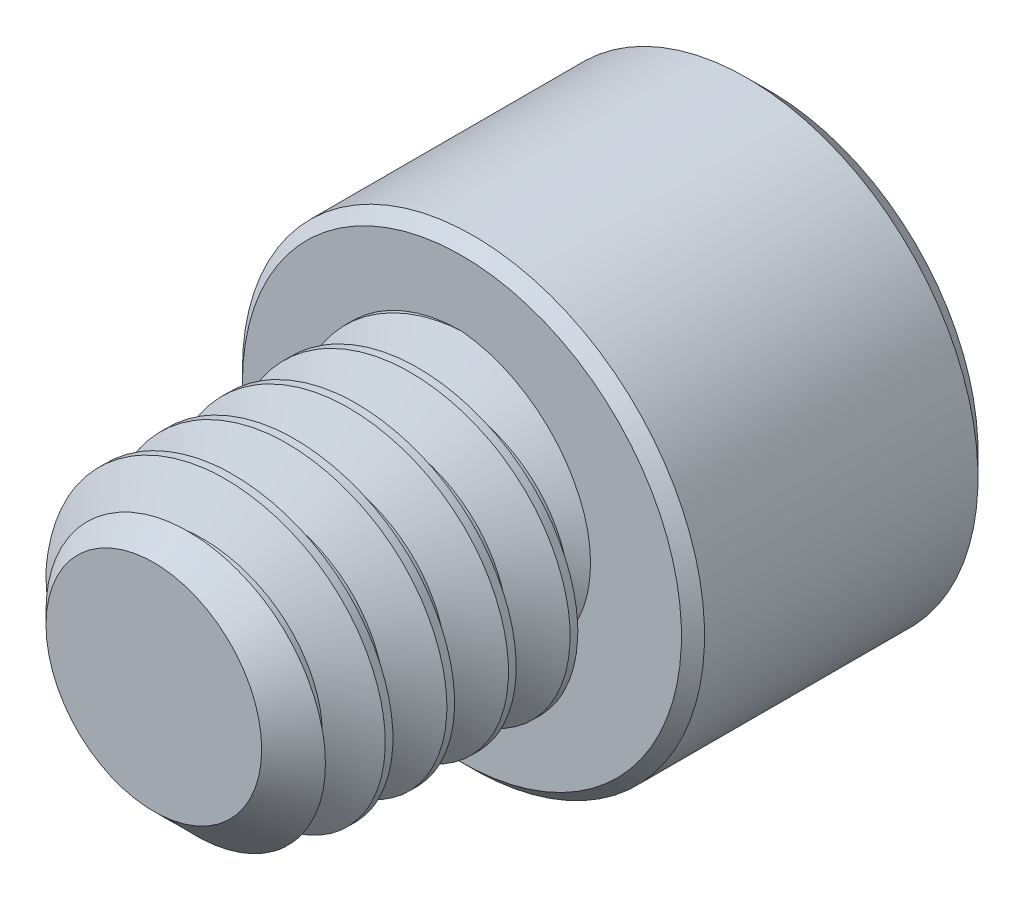
SolidWorks part; units mm, degrees
ref_plane "Front Plane" through (0, 0, 0) normal (0, 0, 1) x (1, 0, 0)
ref_plane "Top Plane" through (0, 0, 0) normal (0, 1, 0) x (1, 0, 0)
ref_plane "Right Plane" through (0, 0, 0) normal (1, 0, 0) x (0, 0, -1)
sketch "Sketch0" plane through (0, 0, 0) normal (1, 0, 0) x (0, 0, -1)
  line L0 (0, 0) -> (6.35, 0) construction
  point P2 (12.7, 0)
  point P4 (0, 0)
  dimension "D1" = 6.35
  dimension "D2" = 6.35
  dimension "Min Thread" = 0
sketch "Sketch1" plane through (0, 0, 0) normal (0, 0, 1) x (1, 0, 0)
  circle A0 centre (0, 0) radius 3.175
  dimension "OD" = 6.35
extrude "Extrude1" add sketch "Sketch1" against normal blind 6.35
sketch "Sketch2" plane through (0, 0, 0) normal (0, 0, 1) x (1, 0, 0)
  circle A0 centre (0, 0) radius 3.175 construction
  circle A1 centre (0, 0) radius 3.175
curve "Helix/Spiral1" pitch 1.27 height 7.62 turns 6 parameters "pitch"=1.27
chamfer "Chamfer3" distance 0.9525 angle 45 1 edges at (3.175, 0, 0)
sketch "Sketch3" plane through (0, 0, 0) normal (1, 0, 0) x (0, 0, -1)
  line L0 (-1.1113, 3.175) -> (-0.635, 2.3501)
  line L1 (-0.635, 2.3501) -> (-0.4763, 2.3501)
  line L2 (-0.4763, 2.3501) -> (0, 3.175)
  line L3 (-1.1113, 3.175) -> (0, 3.175)
  line L4 (-0.5556, 3.175) -> (-0.5556, 2.3501) construction
  line L5 (-0.8731, 2.7626) -> (-0.2381, 2.7626) construction
  line L6 (0, 3.175) -> (0, -3.175) construction
  dimension "D1" = 0.1588
  dimension "D2" = 0.635
  dimension "D3" = 60
sweep "Cut-Sweep1" cut profiles "Sketch3" path "Helix/Spiral1"
sketch "Sketch5" plane through (0, 0, 0) normal (1, 0, 0) x (0, 0, -1)
  line L0 (6.35, -2.3728) -> (6.35, 2.2654) construction
  line L1 (6.35, 3.175) -> (0, 3.175)
  line L2 (6.35, 3.175) -> (6.35, 0)
  line L3 (6.35, 0) -> (-1.1556, 0)
  line L4 (0, 0) -> (6.35, 0) construction
  line L5 (0, 3.175) -> (-1.1556, 0)
  line L6 (0, 0) -> (8.89, 0) construction
  dimension "D1" = 70
  dimension "D3" = 2.54
revolve "partially thread" [suppressed] add sketch "Sketch5" angle 360 about L6
sketch "Sketch6" plane through (0, 0, -6.35) normal (0, 0, -1) x (-1, 0, 0)
  circle A0 centre (0, 0) radius 4.7625
  dimension "head dia" = 9.525
extrude "Extrude2" add sketch "Sketch6" along normal blind 6.35
sketch "Sketch7" plane through (0, 0, -12.7) normal (0, 0, -1) x (-1, 0, 0)
  line L1 (0, 2.7496) -> (-2.3813, 1.3748)
  line L2 (-2.3813, 1.3748) -> (-2.3813, -1.3748)
  line L3 (-2.3813, -1.3748) -> (0, -2.7496)
  line L4 (0, -2.7496) -> (2.3813, -1.3748)
  line L5 (2.3813, -1.3748) -> (2.3813, 1.3748)
  line L6 (2.3813, 1.3748) -> (0, 2.7496)
  circle A0 centre (0, 0) radius 2.3813 construction
  dimension "hex dia" = 4.7625
extrude "Cut-Extrude1" cut sketch "Sketch7" against normal blind 3.5719
sketch "Sketch8" plane through (0, 0, -12.7) normal (0, 0, -1) x (-1, 0, 0)
  circle A0 centre (0, 0) radius 2.7496
extrude "Cut-Extrude2" cut sketch "Sketch8" against normal through all draft 45
chamfer "Chamfer1" distance 0.4763 angle 45 1 edges at (-4.7625, 0, -12.7)
chamfer "Chamfer2" distance 0.2381 angle 45 1 edges at (-4.7625, 0, -6.35)
sketch "Sketch9" plane through (0, 0, 0) normal (1, 0, 0) x (0, 0, -1)
  line L0 (0, 3.175) -> (0, -3.175) construction
  line L1 (3.175, 3.175) -> (3.175, -3.175) construction
  line L2 (12.7, 4.7625) -> (12.7, -4.7625) construction
  line L3 (6.35, 4.7625) -> (6.35, -4.7625) construction
  line L4 (6.35, 4.5244) -> (6.35, -4.5244) construction
  line L5 (12.7, -4.2863) -> (12.7, 4.2863) construction
  line L6 (6.35, -4.7625) -> (6.35, 4.7625) construction
  line L7 (0, 2.2225) -> (0, -2.2225) construction
  line L8 (-1.1113, 3.175) -> (0, 3.175) construction
  line L9 (3.175, 0) -> (0, 0) construction
  dimension "D1" = 3.175
equation "\"D3@Helix/Spiral1\" = \"screw length@Extrude1\"+\"pitch@Helix/Spiral1\""
equation "\"D1@Sketch3\" = \"pitch@Helix/Spiral1\"*.125"
equation "\"D2@Sketch3\" = \"pitch@Helix/Spiral1\"*.5"
equation "\"D1@Cut-Extrude1\" = \"hex dia@Sketch7\"*.75"
equation "\"D1@Chamfer1\" = \"head dia@Sketch6\"*.05"
equation "\"D1@Sketch9\" = \"pitch@Helix/Spiral1\"*2.50"
equation "\"D1@Chamfer2\" = \"D1@Chamfer1\"/2"
equation "\"D1@Chamfer3\" = \"pitch@Helix/Spiral1\"*.750"
equation "\"D1@Sketch0\" = \"screw length@Extrude1\""
equation "\"D2@Sketch0\" = \"head depth@Extrude2\""
